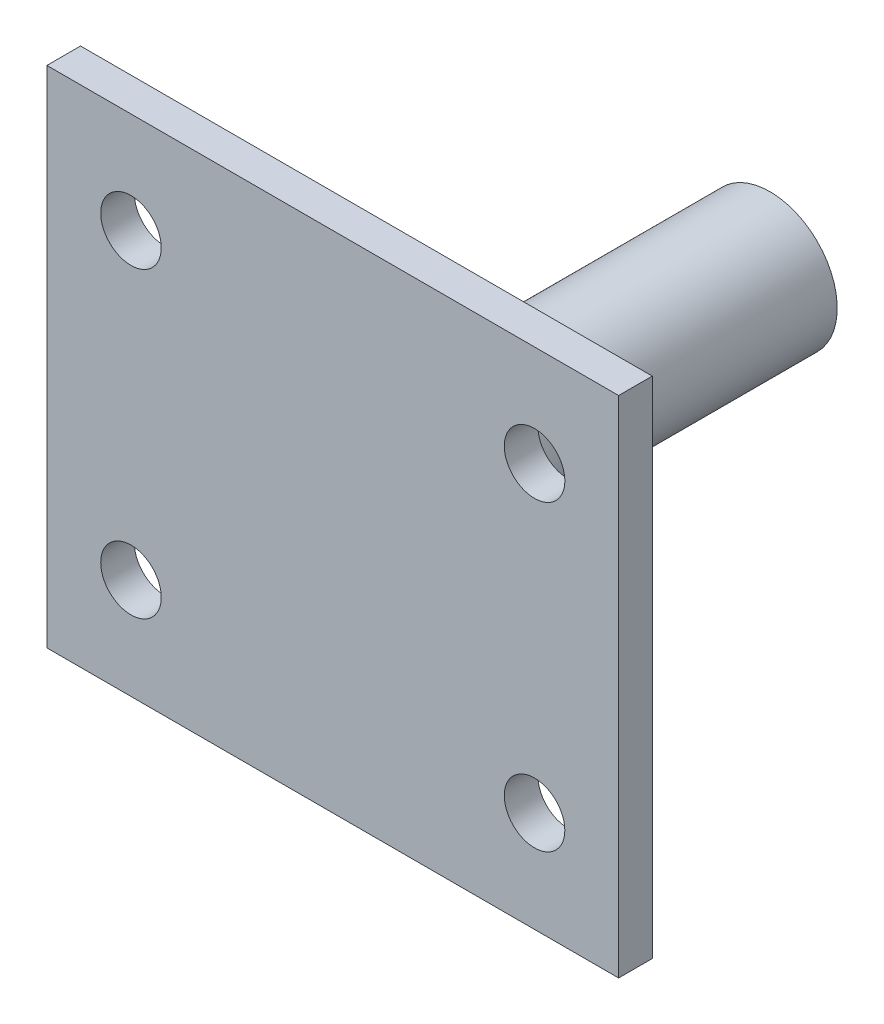
SolidWorks part; units mm, degrees
ref_plane "Front Plane" through (0, 0, 0) normal (0, 0, 1) x (1, 0, 0)
ref_plane "Top Plane" through (0, 0, 0) normal (0, 1, 0) x (1, 0, 0)
ref_plane "Right Plane" through (0, 0, 0) normal (1, 0, 0) x (0, 0, -1)
sketch "Sketch1" plane through (0, 0, 0) normal (0, 0, 1) x (1, 0, 0)
  line L0 (0, 22.04) -> (0, -20.4282) construction
  line L1 (-17, 15) -> (17, 15)
  line L2 (-17, 15) -> (-17, -15)
  line L3 (-17, -15) -> (17, -15)
  line L4 (17, 15) -> (17, -15)
  line L5 (-17, 15) -> (17, -15) construction
  line L6 (-17, -15) -> (17, 15) construction
  line L7 (-31.0989, 0) -> (30.1968, 0) construction
  circle A0 centre (-12, 9) radius 1.8
  circle A1 centre (12, 9) radius 1.8
  circle A2 centre (12, -9) radius 1.8
  circle A3 centre (-12, -9) radius 1.8
  point P0 (0, 0)
  dimension "D5" = 3.6
  dimension "D1" = 34
  dimension "D2" = 30
  dimension "D3" = 12
  dimension "D4" = 24
extrude "Boss-Extrude1" add sketch "Sketch1" along normal blind 2
scale "Scale1" scale about centroid uniform scaling yes scale factor 1.25
sketch "Sketch2" plane through (0, 0, -0.25) normal (0, 0, -1) x (-1, 0, 0)
  circle A1 centre (0, 0) radius 5
  dimension "D1" = 10
extrude "Boss-Extrude2" add sketch "Sketch2" along normal blind 30
